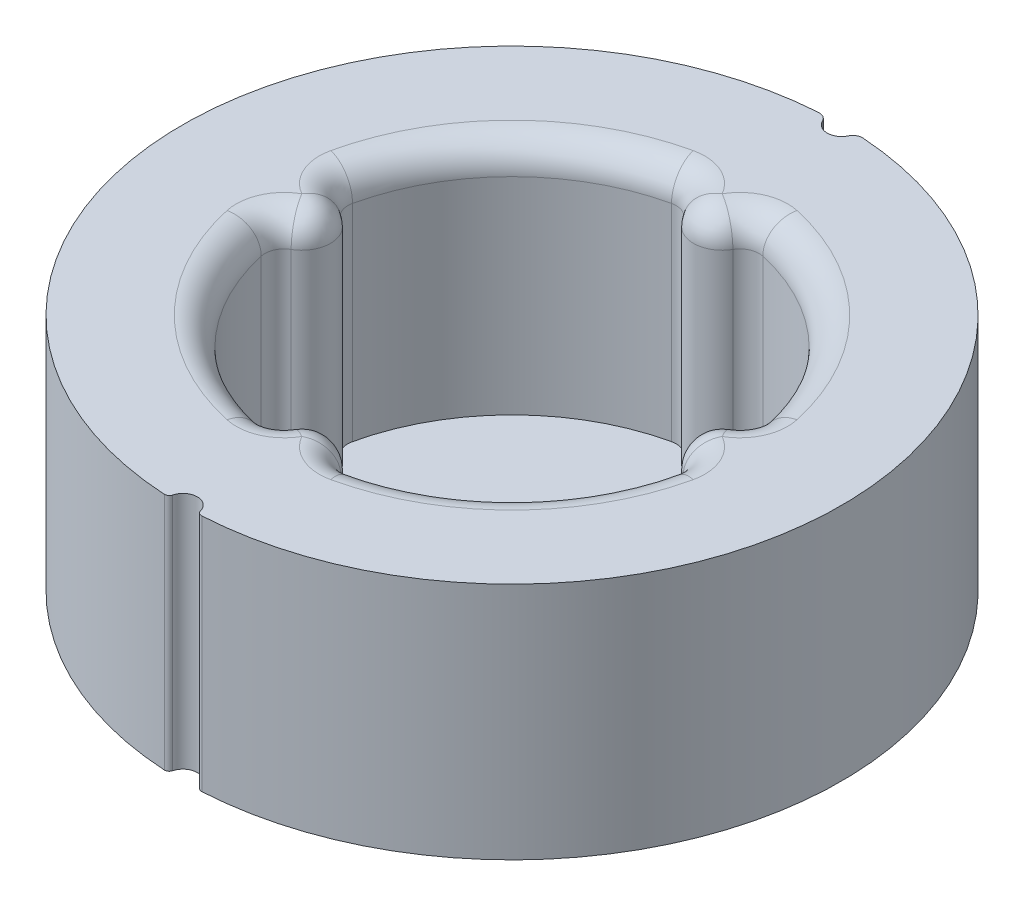
SolidWorks part; units mm, degrees
ref_plane "Front Plane" through (0, 0, 0) normal (0, 0, 1) x (1, 0, 0)
ref_plane "Top Plane" through (0, 0, 0) normal (0, 1, 0) x (1, 0, 0)
ref_plane "Right Plane" through (0, 0, 0) normal (1, 0, 0) x (0, 0, -1)
sketch "Sketch1" plane through (0, 0, 0) normal (0, 1, 0) x (1, 0, 0)
  line L3 (0, 0.002) -> (0, 3.7877) construction
  line L4 (0, 3.7877) -> (2.417, 3.7877)
  line L5 (0, 3.7877) -> (-2.417, 3.7877)
  arc A0 (1.9642, -34.442) -> (34.1982, 4.5552) centre (0, 0.002) ccw
  arc A2 (-2.417, 3.7877) -> (2.417, 3.7877) centre (0, 0.002) ccw
  circle A3 centre (0, 0.002) radius 34.5 construction
  arc A7 (-1.3541, 33.8562) -> (1.3541, 33.8562) centre (0, 34.5015) ccw
  arc A8 (34.1982, 4.5552) -> (2.3241, 34.4236) centre (0, 0.002) ccw
  arc A9 (-2.3241, 34.4236) -> (-34.1982, 4.5552) centre (0, 0.002) ccw
  arc A10 (-34.1982, 4.5552) -> (-1.9642, -34.442) centre (0, 0.002) ccw
  arc A11 (1.3541, 33.8562) -> (2.3241, 34.4236) centre (2.2568, 33.4259) cw
  arc A12 (-1.3541, 33.8562) -> (-2.3241, 34.4236) centre (-2.2568, 33.4259) ccw
  arc A13 (1.4518, -34.0686) -> (-1.4518, -34.0686) centre (0, -34.4457) ccw
  arc A14 (1.4518, -34.0686) -> (1.9642, -34.442) centre (1.9358, -33.9428) ccw
  arc A15 (-1.4518, -34.0686) -> (-1.9642, -34.442) centre (-1.9358, -33.9428) cw
  point P15 (1.4997, 34.4694)
  dimension "D2" = 4.834
  dimension "D3" = 4.4915
  dimension "D4" = 34.5
  dimension "D5" = 1
  dimension "D6" = 1.5
  dimension "D7" = 0.5
  dimension "D11" = 1.4997
sketch "Sketch2" plane through (0, 0, 0) normal (0, 1, 0) x (1, 0, 0)
  arc A0 (-21.475, -4.7775) -> (-4.7775, -21.475) centre (0, 0) ccw
  arc A1 (-2.6059, 20.5136) -> (2.6059, 20.5136) centre (0, 22) ccw
  arc A2 (20.5136, 2.6059) -> (20.5136, -2.6059) centre (22, 0) ccw
  arc A3 (2.6059, -20.5136) -> (-2.6059, -20.5136) centre (0, -22) ccw
  arc A4 (-20.5136, -2.6059) -> (-20.5136, 2.6059) centre (-22, 0) ccw
  arc A5 (-4.7775, 21.475) -> (-21.475, 4.7775) centre (0, 0) ccw
  arc A6 (21.475, 4.7775) -> (4.7775, 21.475) centre (0, 0) ccw
  arc A7 (4.7775, -21.475) -> (21.475, -4.7775) centre (0, 0) ccw
  arc A8 (-20.5136, -2.6059) -> (-21.475, -4.7775) centre (-19.5227, -4.3432) ccw
  arc A9 (-20.5136, 2.6059) -> (-21.475, 4.7775) centre (-19.5227, 4.3432) cw
  arc A10 (2.6059, -20.5136) -> (4.7775, -21.475) centre (4.3432, -19.5227) ccw
  arc A11 (-2.6059, -20.5136) -> (-4.7775, -21.475) centre (-4.3432, -19.5227) cw
  arc A12 (20.5136, 2.6059) -> (21.475, 4.7775) centre (19.5227, 4.3432) ccw
  arc A13 (20.5136, -2.6059) -> (21.475, -4.7775) centre (19.5227, -4.3432) cw
  arc A14 (2.6059, 20.5136) -> (4.7775, 21.475) centre (4.3432, 19.5227) cw
  arc A15 (-2.6059, 20.5136) -> (-4.7775, 21.475) centre (-4.3432, 19.5227) ccw
  point P21 (2.993, -21.7955)
  point P26 (21.7955, 2.993)
  point P33 (-2.993, 21.7955)
  dimension "D1" = 22
  dimension "D2" = 3
  dimension "D3" = 3
  dimension "D4" = 3
  dimension "D5" = 3
  dimension "D6" = 2
extrude "Boss-Extrude1" add sketch "Sketch1" along normal blind 25 contours A10 A0 A8 A7 A9 A2 L5 L4 region at (2.2155, 0, 33.5591)
extrude "Cut-Extrude2" cut sketch "Sketch2" along normal through all
extrude "Boss-Extrude2" add sketch "Sketch2<2>" along normal blind 0.4
sketch "Sketch2<2>" plane through (0, 0, 0) normal (0, 1, 0) x (1, 0, 0) same geometry as "Sketch2"
fillet "Fillet1" radius 3 16 edges at (-21.3515, 25, -3.5336) (-19, 25, 0) (-21.3515, 25, 3.5336) (-15.5563, 25, 15.5563) (-3.5336, 25, 21.3515) (0, 25, 19) (3.5336, 25, 21.3515) (21.3515, 25, 3.5336) (15.5563, 25, 15.5563) (21.3515, 25, -3.5336) (19, 25, 0) (15.5563, 25, -15.5563) (3.5336, 25, -21.3515) (0, 25, -19) (-3.5336, 25, -21.3515) (-15.5563, 25, -15.5563)
